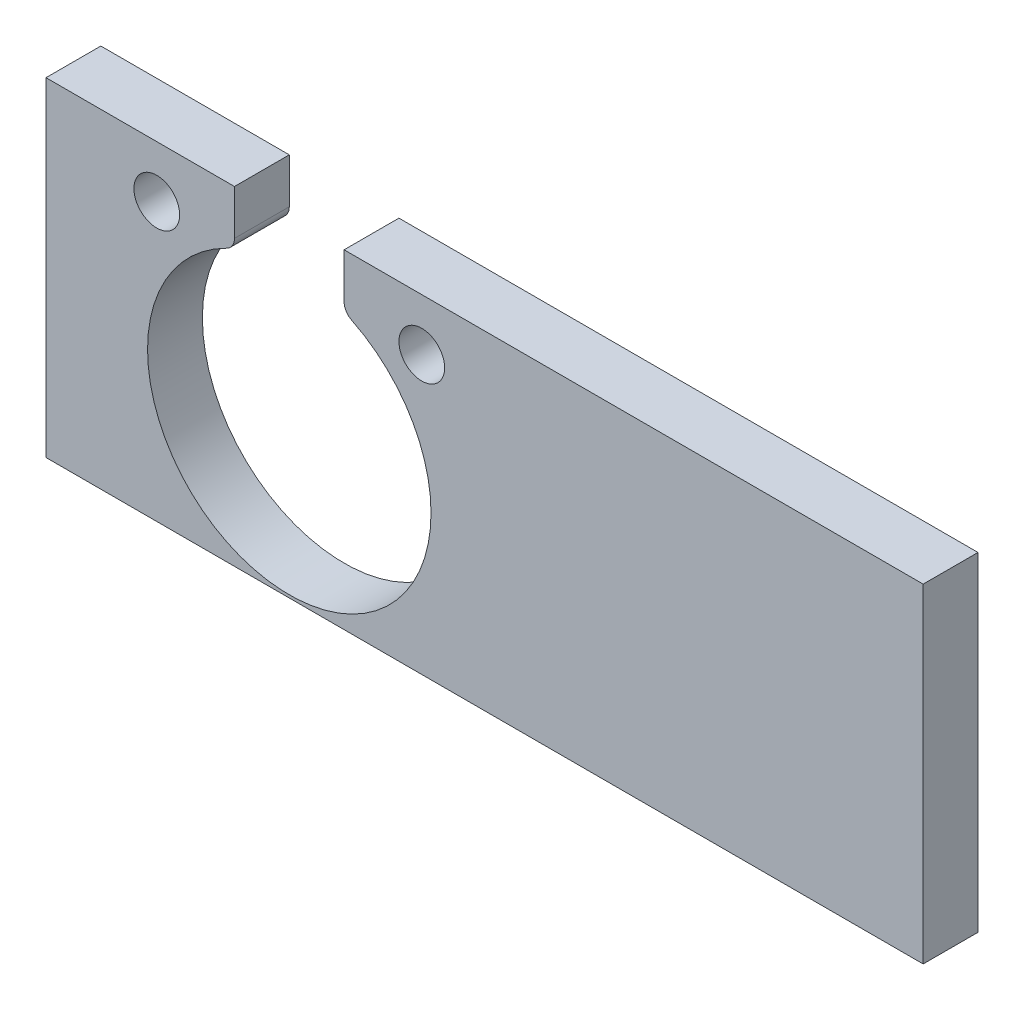
SolidWorks part; units mm, degrees
material "Acrylic (Medium-high impact)"
ref_plane "Front Plane" through (0, 0, 0) normal (0, 0, 1) x (1, 0, 0)
ref_plane "Top Plane" through (0, 0, 0) normal (0, 1, 0) x (1, 0, 0)
ref_plane "Right Plane" through (0, 0, 0) normal (1, 0, 0) x (0, 0, -1)
sketch "Sketch1" plane through (0, 0, 0) normal (0, 0, 1) x (1, 0, 0)
  line L1 (25.1686, 15.8862) -> (-22.8242, 15.8862)
  line L2 (25.1686, 15.8862) -> (25.1686, -2.1138)
  line L3 (25.1686, -2.1138) -> (-22.8242, -2.1138)
  line L4 (-22.8242, 15.8862) -> (-22.8242, -2.1138)
  point P4 (27.1686, 15.8862)
  dimension "D2" = 18
extrude "Boss-Extrude1" add sketch "Sketch1" along normal blind 3
sketch "Sketch2" plane through (0, 0, 0) normal (0, 0, -1) x (-1, 0, 0)
  line L9 (6.5138, 15.8862) -> (12.5127, 15.8862)
  line L11 (6.5138, 15.8862) -> (6.5138, 13.4251)
  line L12 (12.5127, 13.4251) -> (12.5127, 15.8862)
  line L13 (6.5138, 15.8862) -> (6.5138, 13.4251)
  line L14 (12.5127, 13.4251) -> (12.5127, 15.8862)
  circle A26 centre (2.2633, 13.0412) radius 1.25
  circle A27 centre (16.7633, 13.0412) radius 1.25
  arc A29 (12.5127, 13.4251) -> (12.9321, 12.7519) centre (13.2627, 13.4251) ccw
  arc A30 (6.0944, 12.7519) -> (6.5138, 13.4251) centre (5.7638, 13.4251) ccw
  arc A31 (6.0944, 12.7519) -> (12.9321, 12.7519) centre (9.5133, 5.7912) ccw
  arc A32 (12.5127, 13.4251) -> (12.9321, 12.7519) centre (13.2627, 13.4251) ccw
  arc A33 (6.0944, 12.7519) -> (6.5138, 13.4251) centre (5.7638, 13.4251) ccw
  arc A34 (6.0944, 12.7519) -> (12.9321, 12.7519) centre (9.5133, 5.7912) ccw
  dimension "D1" = 0.25
extrude "Cut-Extrude1" cut sketch "Sketch2" against normal up to surface (3 mm away) up to face at (1.1722, 6.8862, 3)
